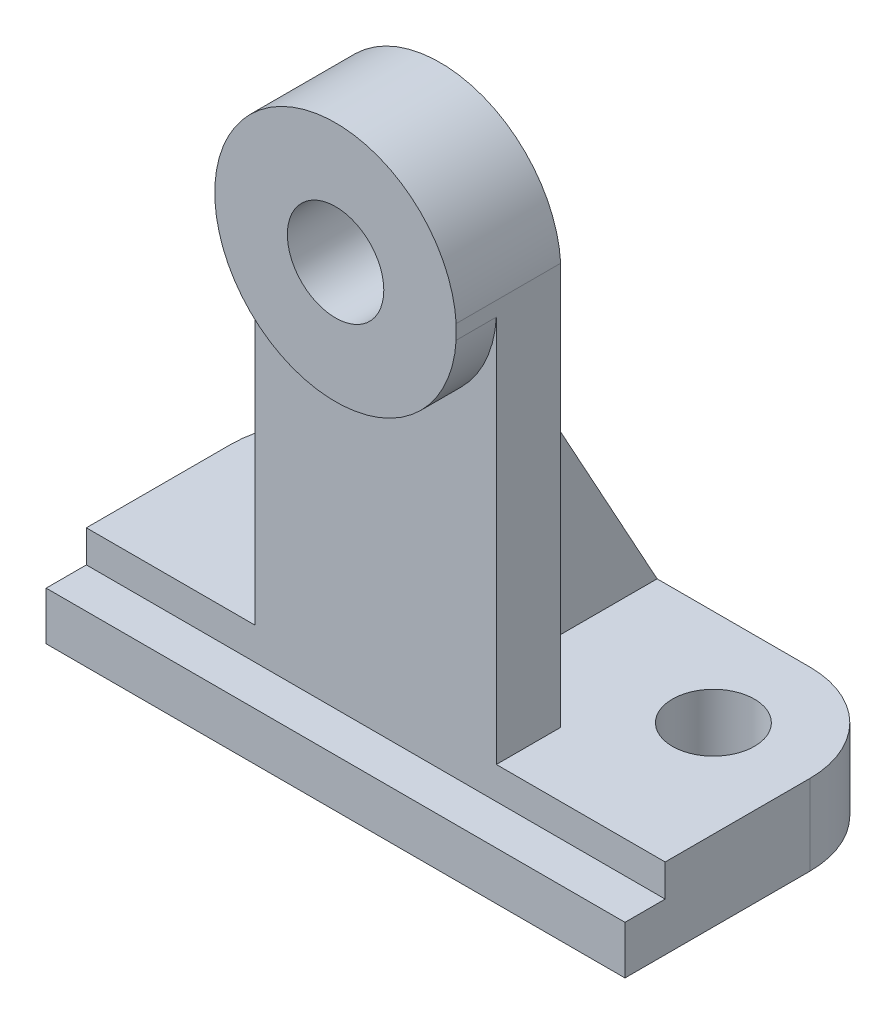
SolidWorks part; units mm, degrees
ref_plane "Front Plane" through (0, 0, 0) normal (0, 0, 1) x (1, 0, 0)
ref_plane "Top Plane" through (0, 0, 0) normal (0, 1, 0) x (1, 0, 0)
ref_plane "Right Plane" through (0, 0, 0) normal (1, 0, 0) x (0, 0, -1)
sketch "Sketch1" plane through (0, 0, 0) normal (0, 0, 1) x (1, 0, 0)
  line L0 (-36, 0) -> (36, 0)
  line L1 (36, 0) -> (36, -10)
  line L2 (36, -10) -> (-36, -10)
  line L3 (-36, -10) -> (-36, 0)
  point P3 (0, 0)
  dimension "D1" = 72
  dimension "D2" = 10
extrude "Boss-Extrude1" add sketch "Sketch1" against normal blind 35
sketch "Sketch2" plane through (36, 0, 0) normal (1, 0, 0) x (0, 0, -1)
  line L0 (0, 0) -> (0, -4)
  line L1 (0, -10) -> (0, 0) construction
  line L2 (0, -4) -> (5, -4)
  line L3 (5, -4) -> (5, 0)
  line L4 (35, 0) -> (0, 0) construction
  line L5 (5, 0) -> (0, 0)
  dimension "D1" = 4
  dimension "D2" = 5
extrude "Cut-Extrude1" cut sketch "Sketch2" against normal through all both
sketch "Sketch4" plane through (0, 0, 0) normal (0, 0, 1) x (1, 0, 0)
  line L0 (-15, 0) -> (15, 0)
  line L1 (-36, 0) -> (36, 0) construction
  line L2 (-15, 0) -> (-15, 50)
  line L4 (15, 50) -> (15, 0)
  circle A1 centre (0, 49.0998) radius 15.027
  point P6 (0, 0)
  dimension "D1" = 30
  dimension "D2" = 50
extrude "Boss-Extrude2" add sketch "Sketch4" against normal blind 8 from offset 5 contours A1 L2 L0 L4 region at (0, 18.7869, 0) offset against normal yes
extrude "Boss-Extrude3" add sketch "Sketch4<5>" against normal blind 13 contours L4 A1 L2 region at (0, 49.0998, 0)
sketch "Sketch4<5>" plane through (0, 0, 0) normal (0, 0, 1) x (1, 0, 0) same geometry as "Sketch4"
sketch "Sketch5" plane through (0, 0, 0) normal (0, 0, 1) x (1, 0, 0)
  circle A0 centre (0, 49.0998) radius 6
  dimension "D1" = 12
extrude "Cut-Extrude2" cut sketch "Sketch5" against normal through all both and the other way through all
sketch "Sketch6" plane through (0, 0, 0) normal (1, 0, 0) x (0, 0, -1)
  line L0 (13, 0) -> (13, 40)
  line L1 (13, 50) -> (13, 0) construction
  line L2 (13, 40) -> (35, 0)
  line L3 (35, 0) -> (13, 0)
  dimension "D1" = 40
extrude "Boss-Extrude4" add sketch "Sketch6" along normal mid plane 10 contours L3 L0 L2
sketch "Sketch7" plane through (0, 0, 0) normal (0, 1, 0) x (1, 0, 0)
  line L0 (-5, 35) -> (-36, 35) construction
  line L1 (-36, 35) -> (-36, 5) construction
  line L3 (36, 35) -> (5, 35) construction
  line L6 (36, 35) -> (36, 5) construction
  line L14 (36, 23) -> (36, 5)
  line L15 (24, 35) -> (5, 35)
  line L16 (-36, 23) -> (-36, 5)
  line L17 (-5, 35) -> (-24, 35)
  line L18 (0, 0) -> (0, 45.98) construction
  line L19 (-24, 45.98) -> (24, 45.98) construction
  line L20 (-24, 45.98) -> (-24, -8.0758) construction
  line L21 (24, 45.98) -> (24, -10.98) construction
  line L22 (-36, 23) -> (-36, 35)
  line L23 (-36, 35) -> (-24, 35)
  line L24 (24, 35) -> (36, 35)
  line L25 (36, 35) -> (36, 23)
  arc A0 (36, 23) -> (24, 35) centre (24, 23) ccw
  arc A1 (-36, 23) -> (-24, 35) centre (-24, 23) cw
  circle A2 centre (-24, 23) radius 5.1
  circle A3 centre (24, 23) radius 5.1
  point P17 (0, 45.98)
  dimension "D1" = 12
  dimension "D2" = 10.2
extrude "Cut-Extrude3" cut sketch "Sketch7" against normal through all both contours A0 L25 L24 | L22 A1 L23 region at (-33.3196, 0, -32.3196) region at (33.3196, 0, -32.3196)
sketch "Sketch8" plane through (0, 0, 0) normal (0, 1, 0) x (1, 0, 0)
  line L0 (-5, 35) -> (-24, 35) construction
  line L1 (-36, 23) -> (-36, 35) construction
  line L2 (-36, 35) -> (-24, 35) construction
  line L3 (-36, 23) -> (-36, 5) construction
  line L4 (24, 35) -> (5, 35) construction
  line L5 (24, 35) -> (36, 35) construction
  line L6 (36, 35) -> (36, 23) construction
  line L7 (36, 23) -> (36, 5) construction
  line L8 (-5, 35) -> (-24, 35)
  line L9 (-36, 23) -> (-36, 35)
  line L10 (-36, 35) -> (-24, 35)
  line L11 (-36, 23) -> (-36, 5)
  line L12 (24, 35) -> (5, 35)
  line L13 (24, 35) -> (36, 35)
  line L14 (36, 35) -> (36, 23)
  line L15 (36, 23) -> (36, 5)
  arc A0 (-24, 35) -> (-36, 23) centre (-24, 23) ccw construction
  circle A1 centre (24, 23) radius 5.1
  circle A2 centre (24, 23) radius 5.1
  circle A3 centre (-24, 23) radius 5.1
  circle A4 centre (-24, 23) radius 5.1
  arc A5 (36, 23) -> (24, 35) centre (24, 23) ccw construction
  arc A6 (-24, 35) -> (-36, 23) centre (-24, 23) ccw
  arc A7 (36, 23) -> (24, 35) centre (24, 23) ccw
  dimension "D1" = 0
  dimension "D2" = 0
extrude "Cut-Extrude4" cut sketch "Sketch8" against normal through all both contours A4 | A2 region at (24, 0, -23) region at (-24, 0, -23)
